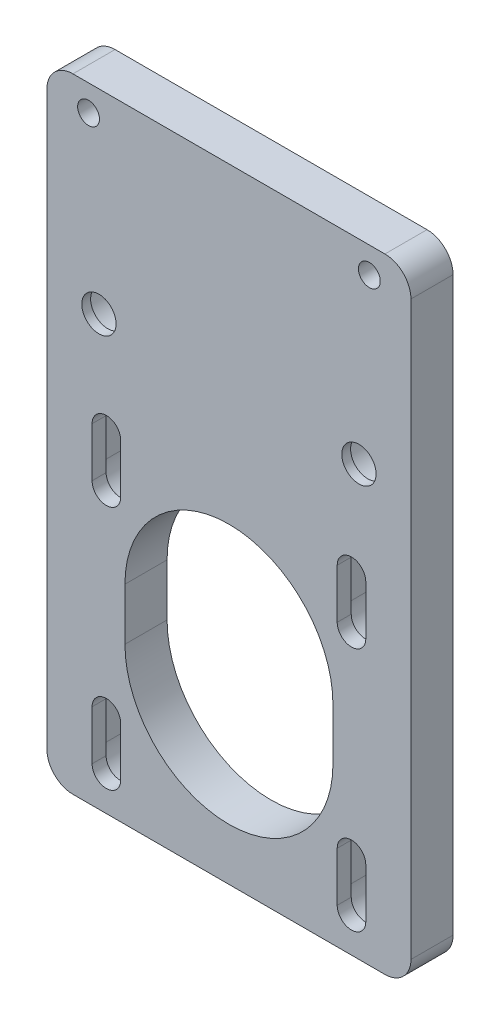
SolidWorks part; units mm, degrees
ref_plane "Plan de face" through (0, 0, 0) normal (0, 0, 1) x (1, 0, 0)
ref_plane "Plan de dessus" through (0, 0, 0) normal (0, 1, 0) x (1, 0, 0)
ref_plane "Plan de droite" through (0, 0, 0) normal (1, 0, 0) x (0, 0, -1)
sketch "Esquisse1" plane through (0, 0, 0) normal (0, 0, 1) x (1, 0, 0)
  line L1 (-35, -60) -> (35, -60)
  line L2 (-35, -60) -> (-35, 60)
  line L3 (-35, 60) -> (35, 60)
  line L4 (35, -60) -> (35, 60)
  line L5 (-35, -60) -> (35, 60) construction
  line L6 (-35, 60) -> (35, -60) construction
  point P0 (0, 0)
  dimension "D1" = 120
  dimension "D2" = 70
extrude "Boss.-Extru.1" add sketch "Esquisse1" along normal blind 8 and the other way blind 0.1
hole_wizard "Chambrage pour vis à tête hexagonale M62" positions "Esquisse2" profile "Esquisse3" counterbore size "M6" standard "ISO" end condition through all
sketch "Esquisse2" plane through (0, 0, -0.1) normal (0, 0, -1) x (-1, 0, 0)
  line L0 (-25, 22.5) -> (25, 22.5) construction
  line L3 (0, 22.5) -> (0, 0) construction
  line L6 (-35, 60) -> (35, 60) construction
  point P7 (-25, 22.5)
  point P9 (25, 22.5)
  dimension "D1" = 50
  dimension "D2" = 37.5
sketch "Esquisse3" plane through (-25, 22.5, -0.1) normal (1, 0, 0) x (0, 1, 0)
  line L0 (0, 0) -> (0, 8.1)
  line L1 (0, 8.1) -> (3.3, 8.1)
  line L3 (3.3, 8.1) -> (3.3, 6.4)
  line L4 (3.3, 6.4) -> (5.5, 6.4)
  line L5 (5.5, 6.4) -> (5.5, 0)
  line L7 (5.5, 0) -> (0, 0)
  line L11 (0, -6.35) -> (0, 107.95) construction
  dimension "Diamètre du perçage jusqu'au prochain" = 6.6
  dimension "Profondeur du perçage jusqu'au prochain" = 8.1
  dimension "Diamètre du chambrage" = 11
  dimension "Profondeur du chambrage" = 6.4
sketch "Esquisse4" plane through (0, 0, 8) normal (0, 0, 1) x (1, 0, 0)
  line L0 (0, 60) -> (0, -60) construction
  line L1 (35, 60) -> (-35, 60) construction
  line L2 (-35, -60) -> (35, -60) construction
  line L3 (0, -20) -> (0, -30) construction
  line L4 (20, -20) -> (20, -30)
  line L5 (-20, -20) -> (-20, -30)
  line L6 (35, 60) -> (-35, 60) construction
  circle A0 centre (0, -20) radius 20
  arc A1 (20, -20) -> (-20, -20) centre (0, -20) ccw
  arc A2 (-20, -30) -> (20, -30) centre (0, -30) ccw
  point P8 (0, -25)
  dimension "D1" = 40
  dimension "D3" = 10
  dimension "D2" = 80
extrude "Enlèv. mat.-Extru.1" cut sketch "Esquisse4" against normal through all contours A0 | L5 A2 L4 A0 region at (0, -20, 8) region at (0, -40.708, 8)
hole_wizard "Rainure de chambrage pour vis à tête hexagonale M53" positions "Esquisse14" profile "Esquisse8" size "M5" standard "ISO" slot yes end condition through all
sketch "Esquisse14" plane through (0, 0, -0.1) normal (0, 0, -1) x (-1, 0, 0)
  line L1 (-23.57, -43.57) -> (23.57, -43.57)
  line L2 (-23.57, -43.57) -> (-23.57, 3.57)
  line L3 (-23.57, 3.57) -> (23.57, 3.57)
  line L4 (23.57, -43.57) -> (23.57, 3.57)
  line L5 (-23.57, -43.57) -> (23.57, 3.57) construction
  line L6 (-23.57, 3.57) -> (23.57, -43.57) construction
  line L7 (-23.57, -8.68) -> (-23.57, 6.32) construction
  line L8 (23.57, -23.93) -> (23.57, 31.07) construction
  line L9 (-16.07, -29.2253) -> (-31.07, -29.2253) construction
  line L10 (-23.57, -8.68) -> (-23.57, 6.32) construction
  line L13 (-35, 60) -> (35, 60) construction
  circle A1 centre (-23.57, -5.93) radius 2.75
  circle A2 centre (-23.57, 3.57) radius 2.75
  point P127 (-23.57, -1.18)
  point P131 (-23.57, -48.32)
  point P133 (23.57, -48.32)
  point P135 (23.57, -1.18)
  point P189 (0, -20)
  dimension "D6" = 5.5
  dimension "D1" = 15
  dimension "D2" = 47.14
  dimension "D3" = 15
  dimension "D4" = 15
  dimension "D5" = 47.14
  dimension "D8" = 80
  dimension "D7" = 2
sketch "Esquisse8" plane through (-23.57, -1.18, -0.1) normal (1, 0, 0) x (0, 1, 0)
  line L0 (0, 0) -> (0, 8.1)
  line L1 (0, 8.1) -> (2.75, 8.1)
  line L3 (2.75, 8.1) -> (2.75, 5.4)
  line L4 (5, 5.4) -> (2.75, 5.4)
  line L5 (5, 5.4) -> (5, 0.025)
  line L6 (5, 0.025) -> (5.025, 0)
  line L7 (5.025, 0) -> (0, 0)
  line L8 (-5, 0.025) -> (-5.025, 0) construction
  line L11 (0, -6.35) -> (0, 107.95) construction
  dimension "Diamètre du perçage jusqu'au prochain" = 5.5
  dimension "Profondeur du perçage jusqu'au prochain" = 8.1
  dimension "Diamètre du chambrage" = 10
  dimension "Profondeur du chambrage" = 5.4
  dimension "Diamètre du fraisage entrant" = 10.05
  dimension "Angle du fraisage entrant" = 90
sketch "Esquisse15" plane through (0, 0, -0.1) normal (0, 0, -1) x (-1, 0, 0)
  line L0 (-35, 60) -> (-35, 66) construction
  line L1 (-27, 55) -> (27, 55) construction
  line L2 (-35, 60) -> (35, 60) construction
  line L3 (-35, -60) -> (-35, 60) construction
  line L4 (35, 60) -> (35, -60) construction
  line L5 (-35, 66) -> (34.7676, 66) construction
  line L6 (34.7676, 66) -> (35, 60) construction
  line L7 (27, 63) -> (34.8838, 63) construction
  circle A0 centre (27, 55) radius 8
  circle A1 centre (-27, 55) radius 8
  dimension "D1" = 16
  dimension "D4" = 8
  dimension "D2" = 3
  dimension "D3" = 8
  dimension "D5" = 6
hole_wizard "Trou pour taraudage pour trou taraudé M51" positions "Esquisse16" profile "Esquisse18" hole size "M5" standard "ISO" end condition through all
sketch "Esquisse16" plane through (0, 0, -0.1) normal (0, 0, -1) x (-1, 0, 0)
  point P0 (-27, 55)
  point P3 (27, 55)
sketch "Esquisse18" plane through (27, 55, -0.1) normal (1, 0, 0) x (0, 1, 0)
  line L0 (0, 0) -> (0, 8.1)
  line L1 (0, 8.1) -> (2.1, 8.1)
  line L2 (2.1, 8.1) -> (2.1, 0)
  line L5 (2.1, 0) -> (0, 0)
  line L11 (0, -6.35) -> (0, 107.95) construction
  dimension "Diamètre du perçage jusqu'au prochain" = 4.2
  dimension "Profondeur du perçage jusqu'au prochain" = 8.1
fillet "Congé1" radius 5 4 edges at (-35, 60, 3.95) (35, 60, 3.95) (35, -60, 3.95) (-35, -60, 3.95)
